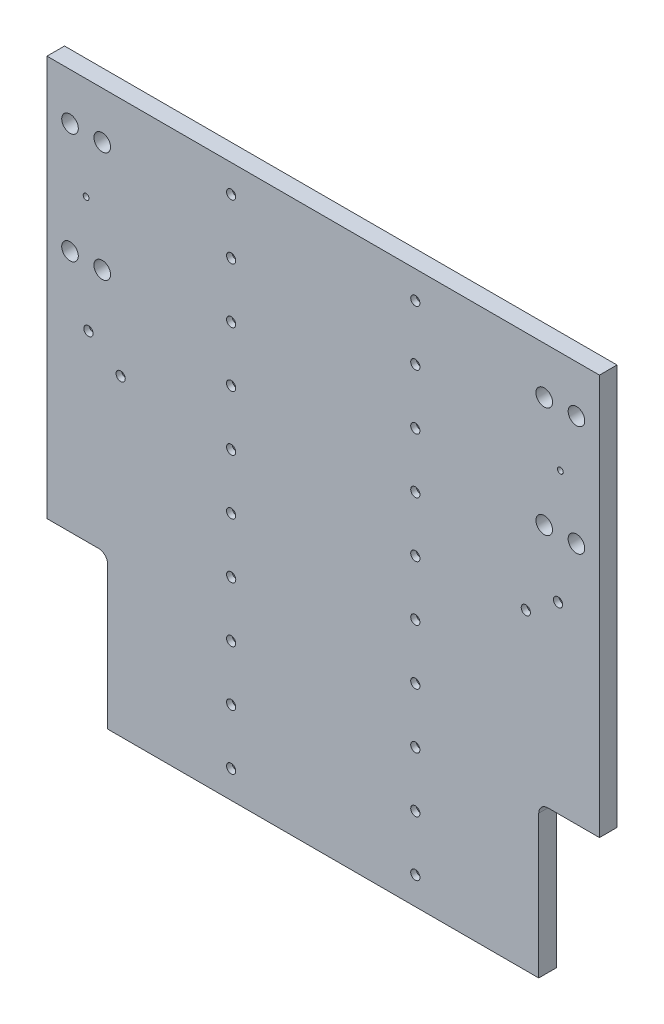
SolidWorks part; units mm, degrees
ref_plane "Front Plane" through (0, 0, 0) normal (0, 0, 1) x (1, 0, 0)
ref_plane "Top Plane" through (0, 0, 0) normal (0, 1, 0) x (1, 0, 0)
ref_plane "Right Plane" through (0, 0, 0) normal (1, 0, 0) x (0, 0, -1)
sketch "Sketch1" plane through (0, 0, 0) normal (0, 0, 1) x (1, 0, 0)
  line L1 (-300, 300) -> (300, 300)
  line L2 (-300, 300) -> (-300, -300)
  line L3 (-300, -300) -> (300, -300)
  line L4 (300, 300) -> (300, -300)
  dimension "D1" = 600
extrude "Boss-Extrude1" add sketch "Sketch1" along normal blind 19.05
sketch "Sketch2" plane through (0, 0, 0) normal (0, 0, -1) x (-1, 0, 0)
  line L0 (300, -300) -> (-300, -300) construction
  line L1 (300, 300) -> (300, -300) construction
  line L2 (234.05, -135) -> (300, -135) construction
  line L3 (234.05, -300) -> (234.05, -125) construction
  line L4 (-234.05, -125) -> (-234.05, -300) construction
  line L5 (-234.05, -135) -> (-300, -135) construction
  line L6 (300, -300) -> (234.05, -300)
  line L7 (300, -135) -> (300, -300)
  line L8 (234.05, -135) -> (300, -135)
  line L9 (234.05, -300) -> (234.05, -135)
  line L10 (-234.05, -135) -> (-234.05, -300)
  line L11 (-234.05, -135) -> (-300, -135)
  line L12 (-234.05, -300) -> (-300, -300)
  line L13 (-300, -135) -> (-300, -300)
extrude "Cut-Extrude1" cut sketch "Sketch2" against normal through all
fillet "Fillet1" radius 10 2 edges at (-234.05, -135, 9.525) (234.05, -135, 9.525)
hole_wizard "CBORE for M5 SHCS1" positions "Sketch3" profile "Sketch4" counterbore size "M5" standard "ANSI Metric"
sketch "Sketch3" plane through (0, 0, 19.05) normal (0, 0, 1) x (1, 0, 0)
  point P0 (-100, 210)
  point P3 (-100, 270)
  point P6 (100, 270)
  point P9 (100, 210)
  point P12 (100, 150)
  point P15 (-100, 150)
  point P18 (-100, 90)
  point P21 (100, 90)
  point P24 (100, 30)
  point P27 (-100, 30)
  point P30 (-255, 64)
  point P33 (-220, 39)
  point P36 (255, 64)
  point P39 (220, 39)
  point P42 (100, -30)
  point P45 (-100, -30)
  point P48 (-100, -90)
  point P51 (100, -90)
  point P54 (100, -150)
  point P57 (-100, -150)
  point P60 (-100, -210)
  point P63 (100, -210)
  point P66 (100, -270)
  point P69 (-100, -270)
sketch "Sketch4" plane through (-100, 210, 19.05) normal (1, 0, 0) x (0, -1, 0)
  line L0 (0, 0) -> (0, 30)
  line L1 (0, 30) -> (2.75, 28.3476)
  line L2 (2.75, 28.3476) -> (2.75, 6)
  line L3 (2.75, 6) -> (5, 6)
  line L4 (5, 6) -> (5, 0)
  line L5 (5, 0) -> (0, 0)
  line L10 (0, 30) -> (-2.75, 28.3476) construction
  line L11 (0, -6.35) -> (0, 107.95) construction
  dimension "Hole Dia." = 5.5
  dimension "Hole Depth" = 30
  dimension "C'Bore Dia." = 10
  dimension "C'Bore Depth" = 6
  dimension "Drill Angle" = 118
sketch "Sketch5" plane through (0, 0, 0) normal (0, 0, -1) x (-1, 0, 0)
  circle A0 centre (240, 249) radius 9.017 construction
  circle A1 centre (275, 249) radius 9.017 construction
  circle A2 centre (257.5, 189) radius 3.175 construction
  circle A3 centre (275, 129) radius 9.017 construction
  circle A4 centre (240, 129) radius 9.017 construction
  circle A5 centre (-275, 129) radius 9.017 construction
  circle A6 centre (-240, 129) radius 9.017 construction
  circle A7 centre (-257.5, 189) radius 3.175 construction
  circle A8 centre (-275, 249) radius 9.017 construction
  circle A9 centre (-240, 249) radius 9.017 construction
  circle A10 centre (240, 249) radius 9.017
  circle A11 centre (275, 249) radius 9.017
  circle A12 centre (257.5, 189) radius 3.175
  circle A13 centre (275, 129) radius 9.017
  circle A14 centre (240, 129) radius 9.017
  circle A15 centre (-275, 129) radius 9.017
  circle A16 centre (-240, 129) radius 9.017
  circle A17 centre (-257.5, 189) radius 3.175
  circle A18 centre (-275, 249) radius 9.017
  circle A19 centre (-240, 249) radius 9.017
extrude "Cut-Extrude2" cut sketch "Sketch5" against normal through all
